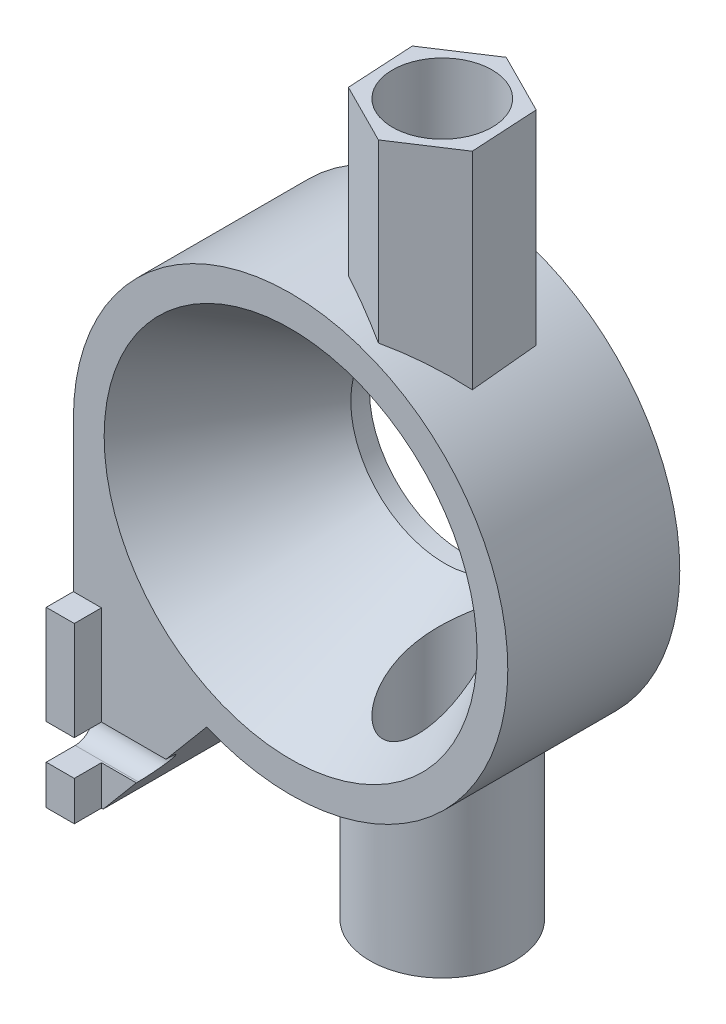
SolidWorks part; units mm, degrees
ref_plane "Front Plane" through (0, 0, 0) normal (0, 0, 1) x (1, 0, 0)
ref_plane "Top Plane" through (0, 0, 0) normal (0, 1, 0) x (1, 0, 0)
ref_plane "Right Plane" through (0, 0, 0) normal (1, 0, 0) x (0, 0, -1)
sketch "Sketch1" plane through (0, 0, 0) normal (0, 0, 1) x (1, 0, 0)
  line L0 (254.309, 185.0586) -> (255.9795, 135.0866) construction
  dimension "D1" = 50
sketch "Sketch3" plane through (0, 0, 0) normal (0, 0, 1) x (1, 0, 0)
  circle A0 centre (225, 142.5) radius 24
  dimension "D1" = 48
extrude "Boss-Extrude1" add sketch "Sketch3" along normal blind 19
sketch "Sketch5" plane through (0, 0, 0) normal (0, 0, 1) x (1, 0, 0)
  line L0 (201, 142.5) -> (201, 106.7745)
  line L1 (201, 106.7745) -> (204.2866, 106.7745)
  line L2 (204.2866, 106.7745) -> (215.7335, 120.3611)
  circle A0 centre (225, 142.5) radius 24 construction
  circle A3 centre (225, 142.5) radius 24
  arc A4 (201, 142.5) -> (215.7335, 120.3611) centre (225, 142.5) ccw
  dimension "D1" = 0
extrude "Boss-Extrude2" add sketch "Sketch5" along normal blind 19
ref_plane "Plane1" through (0, 0, 10) normal (0, 0, 1) x (1, 0, 0)
ref_plane "Plane2" through (0, 118.5, 0) normal (0, -1, 0) x (-1, 0, 0)
ref_plane "Plane3" through (0, 128.5, 0) normal (0, -1, 0) x (-1, 0, 0)
sketch "Sketch7" plane through (0, 128.5, 0) normal (0, -1, 0) x (-1, 0, 0)
  line L1 (-240.76, 10.454) -> (-240.76, -27.7584) construction
  line L4 (-26.8798, -10) -> (26.8798, -10) construction
  line L5 (-201, -19) -> (-201, 0) construction
  circle A1 centre (-232.76, -10) radius 8
  dimension "D1" = 16
  dimension "D2" = 39.76
extrude "Boss-Extrude3" add sketch "Sketch7" along normal blind 22.5
ref_plane "Plane4" through (0, 158.5, 0) normal (0, -1, 0) x (-1, 0, 0)
sketch "Sketch8" plane through (0, 158.5, 0) normal (0, -1, 0) x (-1, 0, 0)
  line L1 (-239.0279, -5.8947) -> (-239.4492, -13.3755)
  line L2 (-239.4492, -13.3755) -> (-233.1813, -17.4808)
  line L3 (-233.1813, -17.4808) -> (-226.4921, -14.1053)
  line L4 (-226.4921, -14.1053) -> (-226.0708, -6.6245)
  line L5 (-226.0708, -6.6245) -> (-232.3387, -2.5192)
  line L6 (-232.3387, -2.5192) -> (-239.0279, -5.8947)
  circle A0 centre (-232.76, -10) radius 6.4888 construction
  circle A1 centre (-232.76, -10) radius 8 construction
extrude "Boss-Extrude4" add sketch "Sketch8" against normal blind 26
sketch "Sketch9" plane through (201, 0, 0) normal (-1, 0, 0) x (0, 0, 1)
  line L0 (0, 142.5) -> (0, 106.7745) construction
  line L1 (19, 106.7745) -> (22, 106.7745)
  line L2 (19, 106.7745) -> (19, 125.9445)
  line L3 (19, 125.9445) -> (22, 125.9445)
  line L4 (22, 106.7745) -> (22, 125.9445)
  dimension "D1" = 22
  dimension "D2" = 19.17
extrude "Boss-Extrude5" add sketch "Sketch9" against normal blind 3.1
sketch "Sketch10" plane through (201, 0, 0) normal (-1, 0, 0) x (0, 0, 1)
  line L0 (5.15, 113.0695) -> (5.15, 122.2677) construction
  line L1 (16.85, 113.0695) -> (16.85, 122.2677) construction
  line L2 (11, 127.8393) -> (11, 106.4652) construction
  line L3 (0, 142.5) -> (0, 106.7745) construction
  line L4 (22, 106.7745) -> (22, 125.9445) construction
  line L5 (3.205, 111.1245) -> (18.795, 111.1245) construction
  line L6 (22, 106.7745) -> (0, 106.7745) construction
  line L9 (0, 142.5) -> (0, 106.7745)
  line L10 (0, 115.0145) -> (0, 111.1245)
  line L11 (3.205, 115.0145) -> (0, 115.0145)
  line L12 (22, 106.7745) -> (22, 125.9445)
  line L13 (22, 111.1245) -> (22, 115.0145)
  line L14 (3.205, 111.1245) -> (0, 111.1245)
  line L15 (18.795, 115.0145) -> (22, 115.0145)
  line L16 (18.795, 111.1245) -> (22, 111.1245)
  arc A0 (3.205, 111.1245) -> (3.205, 115.0145) centre (3.205, 113.0695) ccw
  arc A1 (18.795, 115.0145) -> (18.795, 111.1245) centre (18.795, 113.0695) ccw
  dimension "D3" = 3.89
  dimension "D1" = 11.7
  dimension "D2" = 4.35
  dimension "D4" = 0
  dimension "D5" = 0
extrude "Cut-Extrude1" cut sketch "Sketch10" against normal blind 15
sketch "Sketch15" plane through (0, 0, 0) normal (0, 0, -1) x (-1, 0, 0)
  circle A0 centre (-225, 142.5) radius 21.7
  arc A1 (-201, 142.5) -> (-215.7335, 120.3611) centre (-225, 142.5) ccw construction
  dimension "D1" = 2.3
extrude "Cut-Extrude3" cut sketch "Sketch15" against normal blind 2
sketch "Sketch17" plane through (0, 0, 2) normal (0, 0, -1) x (-1, 0, 0)
  circle A0 centre (-225, 142.5) radius 12.95
  circle A1 centre (-225, 142.5) radius 10.35
  circle A2 centre (-225, 142.5) radius 21.7 construction
  dimension "D1" = 20.7
  dimension "D2" = 25.9
extrude "Boss-Extrude9" add sketch "Sketch17" along normal blind 2.06
ref_axis "Axis3" through (225, 142.5, 19) along (0, 0, -1)
ref_plane "Plane5" through (225, 0, 0) normal (1, 0, 0) x (0, 0, -1)
sketch "Sketch21" plane through (225, 0, 0) normal (1, 0, 0) x (0, 0, -1)
  line L0 (-19, 163.1) -> (-19, 142.5)
  line L1 (-19, 166.5) -> (-19, 118.5) construction
  line L2 (-19, 142.5) -> (-2, 142.5)
  line L3 (-19, 142.5) -> (0, 142.5) construction
  line L6 (-2, 132.15) -> (-2, 152.85) construction
  line L8 (-19, 163.1) -> (-2, 152.85)
  line L10 (-2, 142.5) -> (-2, 152.85)
  dimension "D1" = 3.4
  dimension "D2" = 0
revolve "Cut-Revolve2" cut sketch "Sketch21" angle 360 about axis through (225, 142.5, 19) along (0, 0, -1)
sketch "Sketch24" plane through (0, 106, 0) normal (0, -1, 0) x (1, 0, 0)
  circle A0 centre (232.76, 10) radius 5.5
  circle A1 centre (232.76, 10) radius 8 construction
  dimension "D1" = 11
extrude "Cut-Extrude5" cut sketch "Sketch24" against normal through all
